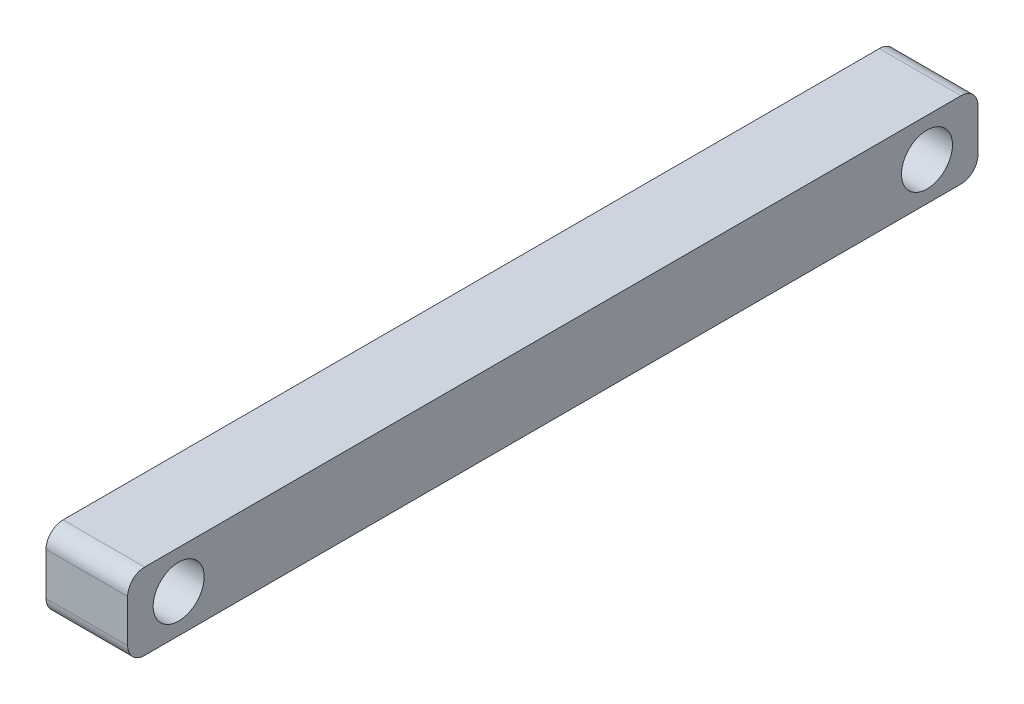
SolidWorks part; units mm, degrees
ref_plane "Alzado" through (0, 0, 0) normal (0, 0, 1) x (1, 0, 0)
ref_plane "Planta" through (0, 0, 0) normal (0, 1, 0) x (1, 0, 0)
ref_plane "Vista lateral" through (0, 0, 0) normal (1, 0, 0) x (0, 0, -1)
sketch "Croquis1" plane through (0, 0, 0) normal (1, 0, 0) x (0, 0, -1)
  line L0 (-24, 2.25) -> (24, 2.25)
  line L2 (-25, 0) -> (25, 0) construction
  line L3 (-25, 1.25) -> (-25, -1.25)
  line L4 (-24, -2.25) -> (24, -2.25)
  line L5 (25, 1.25) -> (25, -1.25)
  arc A0 (-25, -1.25) -> (-24, -2.25) centre (-24, -1.25) ccw
  arc A1 (-25, 1.25) -> (-24, 2.25) centre (-24, 1.25) cw
  arc A2 (24, -2.25) -> (25, -1.25) centre (24, -1.25) ccw
  arc A3 (24, 2.25) -> (25, 1.25) centre (24, 1.25) cw
  point P1 (0, 0)
  point P9 (-25, -2.25)
  point P13 (-25, 2.25)
  point P16 (25, -2.25)
  point P19 (25, 2.25)
  dimension "D3" = 1
  dimension "D4" = 1
  dimension "D1" = 2.25
  dimension "D2" = 50
extrude "Saliente-Extruir1" add sketch "Croquis1" along normal mid plane 4.8
sketch "Croquis2" plane through (0, 0, 0) normal (1, 0, 0) x (0, 0, -1)
  line L0 (-25, 1.25) -> (-25, -1.25) construction
  line L1 (25, -1.25) -> (25, 1.25) construction
  circle A0 centre (-22, 0) radius 1.5
  circle A1 centre (22, 0) radius 1.5
  dimension "D1" = 3
  dimension "D3" = 3
  dimension "D2" = 3
  dimension "D4" = 3
extrude "Cortar-Extruir1" cut sketch "Croquis2" against normal through all both and the other way through all
